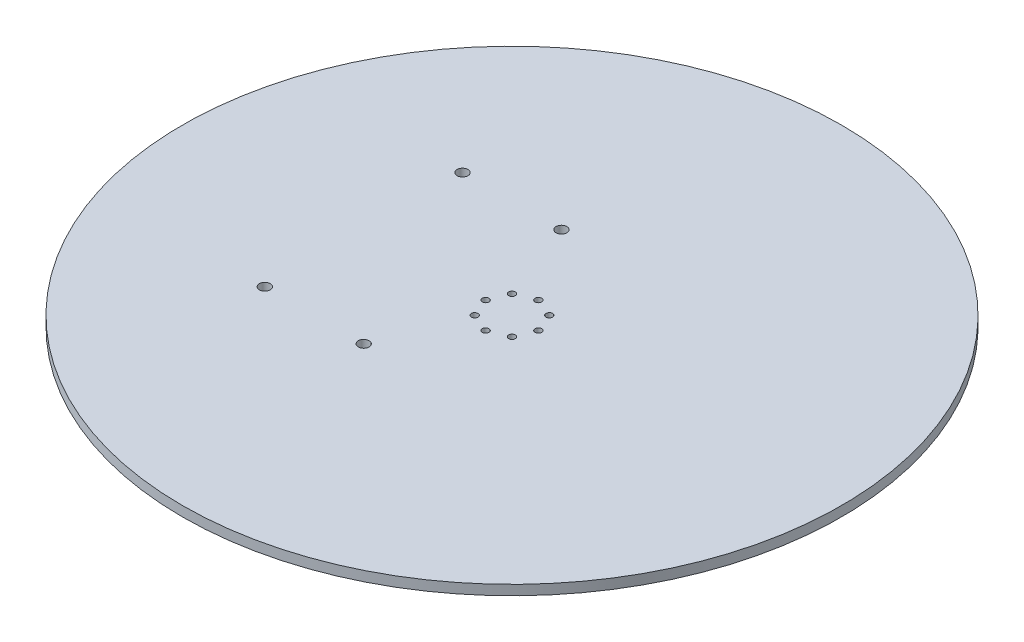
SolidWorks part; units mm, degrees
ref_plane "Front Plane" through (0, 0, 0) normal (0, 0, 1) x (1, 0, 0)
ref_plane "Top Plane" through (0, 0, 0) normal (0, 1, 0) x (1, 0, 0)
ref_plane "Right Plane" through (0, 0, 0) normal (1, 0, 0) x (0, 0, -1)
sketch "Sketch2" plane through (0, 0, 0) normal (0, 1, 0) x (1, 0, 0)
  circle A0 centre (0, 0) radius 100
  dimension "D1" = 200
extrude "Boss-Extrude1" add sketch "Sketch2" along normal blind 3
sketch "Sketch3" plane through (0, 0, 0) normal (0, -1, 0) x (1, 0, 0)
  circle A0 centre (0, 75) radius 10
  dimension "D1" = 75
  dimension "D2" = 20
extrude "Boss-Extrude2" add sketch "Sketch3" along normal blind 4.75
sketch "Sketch4" plane through (0, 0, 0) normal (0, 0, 1) x (1, 0, 0)
  line L0 (0, 3) -> (0, -49997) construction
  line L1 (100, 3) -> (-100, 3) construction
  point P4 (0, 3)
pattern_circular "CirPattern1" count 5 over 360 about axis through (0, 3, 0) along (0, -1, 0) of "Boss-Extrude2"
fillet "Fillet3" radius 10 5 edges at (0, -4.75, 65) (61.8187, -4.75, 20.0861) (38.206, -4.75, -52.5861) (-38.206, -4.75, -52.5861) (-61.8187, -4.75, 20.0861)
sketch "Sketch5" plane through (0, 0, 0) normal (0, -1, 0) x (1, 0, 0)
  line L1 (-0.75, -9.5) -> (0.75, -9.5)
  line L2 (-0.75, -9.5) -> (-0.75, -12.5)
  line L3 (-0.75, -12.5) -> (0.75, -12.5)
  line L4 (0.75, -9.5) -> (0.75, -12.5)
  line L5 (-0.75, -9.5) -> (0.75, -12.5) construction
  line L6 (-0.75, -12.5) -> (0.75, -9.5) construction
  circle A0 centre (0, 0) radius 11
  circle A1 centre (0, 8) radius 1
  circle A2 centre (5.6569, 5.6569) radius 1
  circle A3 centre (8, 0) radius 1
  circle A4 centre (5.6569, -5.6569) radius 1
  circle A5 centre (0, -8) radius 1
  circle A6 centre (-5.6569, -5.6569) radius 1
  circle A7 centre (-8, 0) radius 1
  circle A8 centre (-5.6569, 5.6569) radius 1
  point P5 (0, -11)
  point P22 (0, 0)
  dimension "D1" = 22
  dimension "D2" = 2
  dimension "D3" = 8
  dimension "D5" = 8
  dimension "D6" = 1.5
  dimension "D7" = 3
  dimension "D4" = 8
extrude "Cut-Extrude1" cut sketch "Sketch5" against normal up to surface (3 mm away) contours A8 | A1 | A2 | A3 | A4 | A5 | A6 | A7 up to face at (0, 3, 100)
extrude "Boss-Extrude3" add sketch "Sketch5<3>" along normal blind 3 contours L2 A0 L4 L1 | A0 L2 L3 L4 region at (0, 0, -10.2458) region at (0, 0, -11.7457)
sketch "Sketch5<3>" plane through (0, 0, 0) normal (0, -1, 0) x (1, 0, 0) same geometry as "Sketch5"
sketch "Sketch6" plane through (0, 3, 0) normal (0, 1, 0) x (1, 0, 0)
  line L1 (-45, 30) -> (-15, 30)
  line L2 (-45, 30) -> (-45, -30)
  line L3 (-45, -30) -> (-15, -30)
  line L4 (-15, 30) -> (-15, -30)
  circle A0 centre (-45, 30) radius 2
  circle A1 centre (-15, 30) radius 2
  circle A2 centre (-15, -30) radius 2
  circle A3 centre (-45, -30) radius 2
  point P3 (0, 0)
  point P4 (-15, 0)
  point P8 (0, 0)
  point P9 (0, 0)
  point P15 (0, 0)
  dimension "D4" = 4
  dimension "D1" = 30
  dimension "D2" = 60
  dimension "D3" = 15
  dimension "D5" = 2
  dimension "D6" = 2
hole_wizard "Tap Drill for M4x0.7 Tap1" positions "3DSketch1" profile "Sketch7" hole size "M4x0.7" standard "ANSI Metric" end condition up to next
sketch3d "3DSketch1"
  point P0 (-45, 3, -30)
  point P3 (-15, 3, -30)
  point P6 (-45, 3, 30)
  point P9 (-15, 3, 30)
sketch "Sketch7" plane through (-45, 3, -30) normal (1, 0, 0) x (0, 0, 1)
  line L0 (0, 0) -> (0, 3)
  line L1 (0, 3) -> (1.65, 3)
  line L2 (1.65, 3) -> (1.65, 0)
  line L5 (1.65, 0) -> (0, 0)
  line L11 (0, -6.35) -> (0, 107.95) construction
  dimension "Thru Hole Dia." = 3.3
  dimension "Thru Hole Depth" = 3
